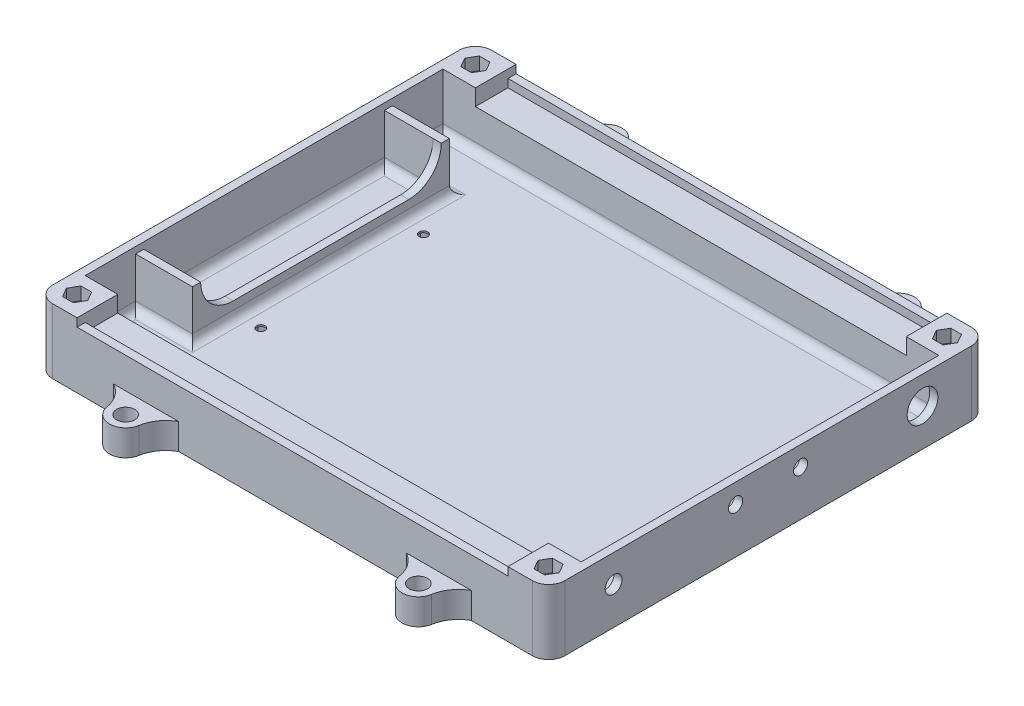
SolidWorks part; units mm, degrees
ref_plane "Front Plane" through (0, 0, 0) normal (0, 0, 1) x (1, 0, 0)
ref_plane "Top Plane" through (0, 0, 0) normal (0, 1, 0) x (1, 0, 0)
ref_plane "Right Plane" through (0, 0, 0) normal (1, 0, 0) x (0, 0, -1)
sketch "Sketch18" plane through (0, 0, 0) normal (0, 1, 0) x (1, 0, 0)
  line L1 (-100.0125, -69.85) -> (100.0125, -69.85)
  line L2 (-100.0125, -69.85) -> (-100.0125, 69.85)
  line L3 (-100.0125, 69.85) -> (100.0125, 69.85)
  line L4 (100.0125, -69.85) -> (100.0125, 69.85)
  line L5 (-100.0125, -69.85) -> (100.0125, 69.85) construction
  line L6 (-100.0125, 69.85) -> (100.0125, -69.85) construction
  point P0 (0, 0)
  dimension "D1" = 139.7
  dimension "D2" = 200.025
extrude "Boss-Extrude6" add sketch "Sketch18" along normal blind 25.4
sketch "Sketch20" plane through (0, 25.4, 0) normal (0, 1, 0) x (1, 0, 0)
  line L0 (100.0125, 69.85) -> (-100.0125, 69.85) construction
  line L1 (96.8375, -69.85) -> (-96.8375, -69.85)
  line L2 (96.8375, -69.85) -> (96.8375, 69.85)
  line L3 (96.8375, 69.85) -> (-96.8375, 69.85)
  line L4 (-96.8375, -69.85) -> (-96.8375, 69.85)
  line L5 (96.8375, -69.85) -> (-96.8375, 69.85) construction
  line L6 (96.8375, 69.85) -> (-96.8375, -69.85) construction
  line L7 (100.0125, -69.85) -> (100.0125, 69.85) construction
  point P0 (0, 0)
  dimension "D1" = 3.175
extrude "Cut-Extrude6" cut sketch "Sketch20" against normal blind 21.59
sketch "Sketch22" plane through (0, 0, 0) normal (0, 1, 0) x (1, 0, 0)
  line L1 (-100.0125, -69.85) -> (100.0125, -69.85)
  line L2 (-100.0125, -69.85) -> (-100.0125, -85.725)
  line L3 (-100.0125, -85.725) -> (100.0125, -85.725)
  line L4 (100.0125, -69.85) -> (100.0125, -85.725)
  dimension "D1" = 15.875
extrude "Boss-Extrude7" add sketch "Sketch22" along normal up to surface (25.4 mm away) up to face at (98.425, 25.4, 0)
sketch "Sketch23" plane through (0, 0, 0) normal (0, 1, 0) x (1, 0, 0)
  line L1 (100.0125, 69.85) -> (-100.0125, 69.85)
  line L2 (100.0125, 69.85) -> (100.0125, 85.725)
  line L3 (100.0125, 85.725) -> (-100.0125, 85.725)
  line L4 (-100.0125, 69.85) -> (-100.0125, 85.725)
  dimension "D1" = 15.875
extrude "Boss-Extrude8" add sketch "Sketch23" along normal up to surface (25.4 mm away) up to face at (0, 25.4, 3.9688)
sketch "Sketch24" plane through (0, 25.4, 0) normal (0, 1, 0) x (1, 0, 0)
  line L6 (100.0125, 85.725) -> (-100.0125, 85.725) construction
  line L8 (-84.1375, -85.725) -> (84.1375, -85.725)
  line L9 (-84.1375, -85.725) -> (-84.1375, 85.725)
  line L10 (-84.1375, 85.725) -> (84.1375, 85.725)
  line L11 (84.1375, -85.725) -> (84.1375, 85.725)
  line L12 (-84.1375, -85.725) -> (84.1375, 85.725) construction
  line L13 (-84.1375, 85.725) -> (84.1375, -85.725) construction
  line L14 (-100.0125, 85.725) -> (-100.0125, -85.725) construction
  point P0 (0, 0)
  dimension "D1" = 15.875
extrude "Cut-Extrude7" cut sketch "Sketch24" against normal blind 3.175
sketch "Sketch28" plane through (0, 22.225, 0) normal (0, 1, 0) x (1, 0, 0)
  line L0 (84.1375, 69.85) -> (-84.1375, 69.85) construction
  line L1 (84.1375, 69.85) -> (-84.1375, 69.85)
  line L2 (84.1375, 69.85) -> (84.1375, 82.55)
  line L3 (84.1375, 82.55) -> (-84.1375, 82.55)
  line L4 (-84.1375, 69.85) -> (-84.1375, 82.55)
  line L5 (84.1375, 69.85) -> (-84.1375, 82.55) construction
  line L6 (84.1375, 82.55) -> (-84.1375, 69.85) construction
  line L7 (-84.1375, 85.725) -> (-84.1375, 69.85) construction
  point P0 (0, 76.2)
  dimension "D1" = 12.7
extrude "Cut-Extrude10" cut sketch "Sketch28" against normal blind 3.175
mirror "Mirror5" about plane through (0, 0, 0) normal (0, 0, 1) of "Cut-Extrude10"
sketch "PCB_Outline" plane through (0, 3.81, 0) normal (0, 1, 0) x (1, 0, 0)
  line L1 (93.6625, -50.8) -> (-73.9775, -50.8)
  line L2 (93.6625, -50.8) -> (93.6625, 50.8)
  line L3 (93.6625, 50.8) -> (-73.9775, 50.8)
  line L4 (-73.9775, -50.8) -> (-73.9775, 50.8)
  line L5 (93.6625, -50.8) -> (-73.9775, 50.8) construction
  line L6 (93.6625, 50.8) -> (-73.9775, -50.8) construction
  line L7 (96.8375, 69.85) -> (-96.8375, 69.85) construction
  line L8 (-96.8375, -69.85) -> (96.8375, -69.85) construction
  line L10 (-66.3575, 31.75) -> (86.0425, 31.75) construction
  line L11 (-66.3575, 31.75) -> (-66.3575, -31.75) construction
  line L12 (-66.3575, -31.75) -> (86.0425, -31.75) construction
  line L13 (86.0425, 31.75) -> (86.0425, -31.75) construction
  line L15 (96.8375, -69.85) -> (96.8375, 69.85) construction
  point P0 (9.8425, 0)
  point P6 (-66.3575, 31.75)
  point P9 (86.0425, 31.75)
  point P12 (86.0425, -31.75)
  point P15 (-66.3575, -31.75)
  dimension "D5" = 3.175
  dimension "D1" = 167.64
  dimension "D2" = 101.6
  dimension "D3" = 152.4
  dimension "D4" = 7.62
  dimension "D6" = 63.5
  dimension "D7" = 19.05
sketch "Sketch31" plane through (0, 3.81, 0) normal (0, 1, 0) x (1, 0, 0)
  circle A0 centre (-66.3575, 31.75) radius 1.65
  circle A1 centre (86.0425, 31.75) radius 1.651
  circle A2 centre (86.0425, -31.75) radius 1.651
  circle A3 centre (-66.3575, -31.75) radius 1.65
  dimension "D1" = 3.3
  dimension "D2" = 3.302
  dimension "D3" = 3.302
  dimension "D4" = 3.3
extrude "Cut-Extrude15" cut sketch "Sketch31" against normal blind 1.825
sketch "Sketch33" plane through (0, 0, 0) normal (0, -1, 0) x (1, 0, 0)
  line L0 (-73.9775, 50.8) -> (-73.9775, -50.8) construction
  line L1 (-63.5575, -33.3666) -> (-63.5575, -30.1334)
  line L2 (-63.5575, -30.1334) -> (-66.3575, -28.5168)
  line L3 (-66.3575, -28.5168) -> (-69.1575, -30.1334)
  line L4 (-69.1575, -30.1334) -> (-69.1575, -33.3666)
  line L5 (-69.1575, -33.3666) -> (-66.3575, -34.9832)
  line L6 (-66.3575, -34.9832) -> (-63.5575, -33.3666)
  line L7 (93.6625, 50.8) -> (93.6625, -50.8) construction
  line L8 (88.8425, -33.3666) -> (88.8425, -30.1334)
  line L9 (88.8425, -30.1334) -> (86.0425, -28.5168)
  line L10 (86.0425, -28.5168) -> (83.2425, -30.1334)
  line L11 (83.2425, -30.1334) -> (83.2425, -33.3666)
  line L12 (83.2425, -33.3666) -> (86.0425, -34.9832)
  line L13 (86.0425, -34.9832) -> (88.8425, -33.3666)
  line L15 (-63.5575, 33.3666) -> (-66.3575, 34.9832)
  line L16 (-66.3575, 34.9832) -> (-69.1575, 33.3666)
  line L17 (-69.1575, 33.3666) -> (-69.1575, 30.1334)
  line L18 (-69.1575, 30.1334) -> (-66.3575, 28.5168)
  line L19 (-66.3575, 28.5168) -> (-63.5575, 30.1334)
  line L20 (-63.5575, 30.1334) -> (-63.5575, 33.3666)
  line L21 (83.2425, 33.3666) -> (83.2425, 30.1334)
  line L22 (83.2425, 30.1334) -> (86.0425, 28.5168)
  line L23 (86.0425, 28.5168) -> (88.8425, 30.1334)
  line L24 (88.8425, 30.1334) -> (88.8425, 33.3666)
  line L25 (88.8425, 33.3666) -> (86.0425, 34.9832)
  line L26 (86.0425, 34.9832) -> (83.2425, 33.3666)
  circle A0 centre (-66.3575, -31.75) radius 2.8 construction
  circle A1 centre (86.0425, -31.75) radius 2.8 construction
  circle A2 centre (-66.3575, 31.75) radius 2.8 construction
  circle A3 centre (86.0425, 31.75) radius 2.8 construction
  dimension "D3" = 5.6
  dimension "D5" = 3.2332
extrude "Cut-Extrude17" cut sketch "Sketch33" against normal blind 3.175
sketch "Sketch39" plane through (0, 25.4, 0) normal (0, 1, 0) x (1, 0, 0)
  line L3 (100.0125, -85.725) -> (100.0125, 85.725) construction
  line L4 (84.1375, 77.7875) -> (92.075, 77.7875) construction
  line L5 (84.1375, 69.85) -> (84.1375, 85.725) construction
  circle A0 centre (92.075, 77.7875) radius 2.2
  dimension "D1" = 4.4
  dimension "D3" = 7.9375
extrude "Cut-Extrude18" cut sketch "Sketch39" against normal blind 26.5
sketch "Sketch41" plane through (0, 25.4, 0) normal (0, 1, 0) x (1, 0, 0)
  line L1 (89.9965, 81.3875) -> (87.9181, 77.7875)
  line L2 (87.9181, 77.7875) -> (89.9965, 74.1875)
  line L3 (89.9965, 74.1875) -> (94.1535, 74.1875)
  line L4 (94.1535, 74.1875) -> (96.2319, 77.7875)
  line L5 (96.2319, 77.7875) -> (94.1535, 81.3875)
  line L6 (94.1535, 81.3875) -> (89.9965, 81.3875)
  circle A0 centre (92.075, 77.7875) radius 3.6 construction
  circle A1 centre (92.075, 77.7875) radius 2.2 construction
  point P1 (92.075, 74.1875)
  dimension "D1" = 7.2
extrude "Cut-Extrude20" cut sketch "Sketch41" against normal blind 5
sketch "Sketch40" plane through (0, 0, 0) normal (0, -1, 0) x (1, 0, 0)
  circle A0 centre (92.075, -77.7875) radius 4.4
  dimension "D1" = 8.8
extrude "Cut-Extrude19" cut sketch "Sketch40" against normal offset from surface (17.225 mm away) 3.175 up to face at (92.075, 20.4, -77.7875)
mirror "Mirror3" about plane through (0, 0, 0) normal (0, 0, 1) of "Cut-Extrude20", "Cut-Extrude19", "Cut-Extrude18"
sketch "Sketch47" plane through (0, 0, 0) normal (0, -1, 0) x (1, 0, 0)
  line L0 (84.1375, -85.725) -> (-84.1375, -85.725) construction
  line L1 (57.15, -100.1441) -> (62.7063, -96.9362) construction
  line L8 (62.7063, -96.9362) -> (62.7063, -90.5204) construction
  line L9 (62.7063, -90.5204) -> (57.15, -87.3125) construction
  line L10 (57.15, -87.3125) -> (51.5938, -90.5204) construction
  line L11 (51.5938, -90.5204) -> (51.5938, -96.9362) construction
  line L12 (51.5938, -96.9362) -> (57.15, -100.1441) construction
  line L13 (57.15, -85.725) -> (57.15, -93.7283) construction
  line L14 (0, -0.0001) -> (0, -85.725) construction
  line L15 (-57.15, -85.725) -> (-57.15, -93.7283) construction
  line L16 (-51.5937, -96.9362) -> (-57.15, -100.1441) construction
  line L17 (-51.5937, -90.5204) -> (-51.5937, -96.9362) construction
  line L18 (-57.15, -87.3125) -> (-51.5937, -90.5204) construction
  line L19 (-62.7062, -90.5204) -> (-57.15, -87.3125) construction
  line L20 (-62.7062, -96.9362) -> (-62.7062, -90.5204) construction
  line L21 (-57.15, -100.1441) -> (-62.7062, -96.9362) construction
  line L22 (0, -0.0001) -> (101.6, -0.0001) construction
  line L40 (-44.45, -85.725) -> (-69.85, -85.725)
  line L41 (69.85, -85.725) -> (44.45, -85.725)
  circle A0 centre (57.15, -93.7283) radius 3.556
  circle A1 centre (57.15, -93.7283) radius 5.5563 construction
  arc A2 (44.45, -85.725) -> (50.887, -94.7756) centre (38.3609, -96.8701) cw
  arc A3 (50.887, -94.7756) -> (57.15, -100.0783) centre (57.15, -93.7283) ccw
  arc A7 (63.413, -94.7756) -> (57.15, -100.0783) centre (57.15, -93.7283) cw
  arc A9 (69.85, -85.725) -> (63.413, -94.7756) centre (75.9391, -96.8701) ccw
  circle A10 centre (-57.15, -93.7283) radius 5.5563 construction
  arc A11 (-69.85, -85.725) -> (-63.413, -94.7756) centre (-75.9391, -96.8701) cw
  arc A12 (-63.413, -94.7756) -> (-57.15, -100.0783) centre (-57.15, -93.7283) ccw
  arc A13 (-50.887, -94.7756) -> (-57.15, -100.0783) centre (-57.15, -93.7283) cw
  arc A14 (-44.45, -85.725) -> (-50.887, -94.7756) centre (-38.3609, -96.8701) ccw
  circle A15 centre (-57.15, -93.7283) radius 3.556
  dimension "D2" = 1.5875
  dimension "D5" = 12.7
  dimension "D3" = 7.112
  dimension "D7" = 25.4
  dimension "D1" = 11.1125
  dimension "D4" = 6.35
  dimension "D6" = 114.3
extrude "Boss-Extrude14" add sketch "Sketch47" against normal blind 10.16
mirror "Mirror4" about plane through (0, 0, 0) normal (0, 0, 1) of "Boss-Extrude14"
mirror "Mirror6" about plane through (0, 0, 0) normal (1, 0, 0) of "Mirror3", "Cut-Extrude18", "Cut-Extrude20", "Cut-Extrude19"
sketch "Sketch48" plane through (96.8375, 0, 0) normal (-1, 0, 0) x (0, 0, 1)
  line L0 (-69.85, 3.81) -> (-69.85, 25.4) construction
  line L1 (-69.85, 3.81) -> (-69.85, 25.4) construction
  line L2 (-69.85, 14.605) -> (-60.325, 14.605) construction
  line L3 (69.85, 3.81) -> (69.85, 25.4) construction
  line L4 (69.85, 3.81) -> (69.85, 25.4) construction
  line L5 (-12.7, 17.78) -> (12.7, 17.78) construction
  line L6 (0, 0) -> (0, 17.78) construction
  line L7 (-85.725, 0) -> (85.725, 0) construction
  circle A0 centre (-60.325, 14.605) radius 6
  circle A1 centre (60.325, 14.605) radius 3.3
  circle A2 centre (-12.7, 17.78) radius 2.75
  circle A3 centre (12.7, 17.78) radius 2.75
  dimension "D1" = 12
  dimension "D2" = 6.6
  dimension "D3" = 5.5
  dimension "D4" = 9.525
  dimension "D5" = 9.525
  dimension "D6" = 3.175
  dimension "D7" = 25.4
extrude "Cut-Extrude21" cut sketch "Sketch48" against normal up to next
sketch "Sketch49" plane through (0, 3.81, 0) normal (0, 1, 0) x (1, 0, 0)
  line L0 (-96.8375, 69.85) -> (-96.8375, -69.85) construction
  line L1 (-96.8375, -45.72) -> (-79.0575, -45.72) construction
  line L2 (-96.8375, -45.72) -> (-96.8375, 45.72) construction
  line L3 (-96.8375, 45.72) -> (-79.0575, 45.72) construction
  line L4 (-79.0575, -45.72) -> (-79.0575, 45.72) construction
  line L5 (-96.8375, -45.72) -> (-79.0575, 45.72) construction
  line L6 (-96.8375, 45.72) -> (-79.0575, -45.72) construction
  line L8 (-77.7875, -46.99) -> (-74.6125, -46.99)
  line L9 (-77.7875, -46.99) -> (-77.7875, 46.99)
  line L10 (-77.7875, 46.99) -> (-74.6125, 46.99)
  line L11 (-74.6125, -46.99) -> (-74.6125, 46.99)
  line L12 (-77.7875, -46.99) -> (-74.6125, 46.99) construction
  line L13 (-77.7875, 46.99) -> (-74.6125, -46.99) construction
  point P0 (-87.9475, 0)
  point P10 (-76.2, 0)
  dimension "D1" = 17.78
  dimension "D2" = 91.44
  dimension "D3" = 93.98
  dimension "D4" = 19.05
  dimension "D5" = 3.175
extrude "Boss-Extrude15" add sketch "Sketch49" along normal blind 6.35
sketch "Sketch50" plane through (0, 3.81, 0) normal (0, 1, 0) x (1, 0, 0)
  line L0 (-96.8375, 69.85) -> (-96.8375, -69.85) construction
  line L1 (-74.6125, 46.99) -> (-96.8375, 46.99)
  line L2 (-74.6125, 46.99) -> (-74.6125, 50.165)
  line L3 (-74.6125, 50.165) -> (-96.8375, 50.165)
  line L4 (-96.8375, 46.99) -> (-96.8375, 50.165)
  line L6 (-74.6125, -46.99) -> (-96.8375, -46.99)
  line L7 (-74.6125, -46.99) -> (-74.6125, -50.165)
  line L8 (-74.6125, -50.165) -> (-96.8375, -50.165)
  line L9 (-96.8375, -46.99) -> (-96.8375, -50.165)
  dimension "D1" = 3.175
extrude "Boss-Extrude16" add sketch "Sketch50" along normal blind 19.05
fillet "Fillet1" radius 6.35 4 edges at (100.0125, 12.7, 85.725) (-100.0125, 12.7, 85.725) (-100.0125, 12.7, -85.725) (100.0125, 12.7, -85.725)
sketch "Battery_Outline" plane through (-96.8375, 0, 0) normal (1, 0, 0) x (0, 0, -1)
  line L0 (46.99, 3.81) -> (-46.99, 3.81) construction
  line L1 (-43.18, 6.35) -> (43.18, 6.35)
  line L2 (-43.18, 6.35) -> (-43.18, 39.37)
  line L3 (-43.18, 39.37) -> (43.18, 39.37)
  line L4 (43.18, 6.35) -> (43.18, 39.37)
  line L5 (-43.18, 6.35) -> (43.18, 39.37) construction
  line L6 (-43.18, 39.37) -> (43.18, 6.35) construction
  line L7 (46.99, 3.81) -> (-46.99, 3.81) construction
  point P0 (0, 22.86)
  dimension "D1" = 33.02
  dimension "D2" = 86.36
  dimension "D3" = 2.54
fillet "Fillet2" radius 3.175 11 edges at (-87.3125, 3.81, -46.99) (-77.7875, 3.81, 0) (-87.3125, 3.81, 46.99) (-96.8375, 3.81, 0) (-96.8375, 3.81, -60.0075) (-85.725, 3.81, -50.165) (-74.6125, 3.81, 0) (-85.725, 3.81, 50.165) (-96.8375, 3.81, 60.0075) (0, 3.81, 69.85) (0, 3.81, -69.85)
fillet "Fillet3" radius 12.7 2 edges at (-76.2, 10.16, 46.99) (-76.2, 10.16, -46.99)
